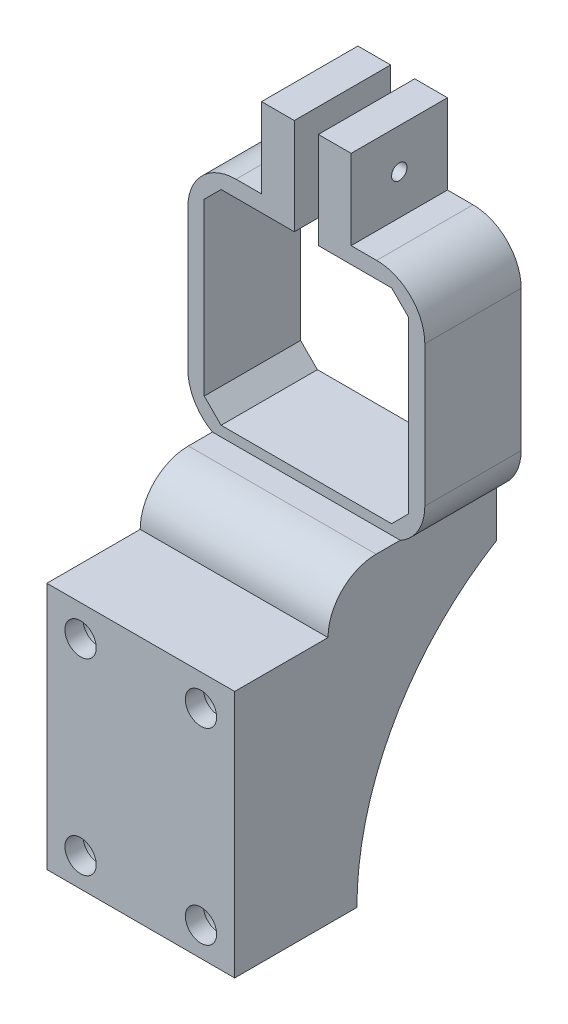
SolidWorks part; units mm, degrees
ref_plane "Front Plane" through (0, 0, 0) normal (0, 0, 1) x (1, 0, 0)
ref_plane "Top Plane" through (0, 0, 0) normal (0, 1, 0) x (1, 0, 0)
ref_plane "Right Plane" through (0, 0, 0) normal (1, 0, 0) x (0, 0, -1)
sketch "Sketch1" plane through (0, 0, 0) normal (0, 0, 1) x (1, 0, 0)
  line L1 (-21.2, -21.2) -> (21.2, -21.2)
  line L2 (-21.2, -21.2) -> (-21.2, 21.2)
  line L3 (-21.2, 21.2) -> (21.2, 21.2)
  line L4 (21.2, -21.2) -> (21.2, 21.2)
  line L5 (-21.2, -21.2) -> (21.2, 21.2) construction
  line L6 (-21.2, 21.2) -> (21.2, -21.2) construction
  line L7 (-24.6, -24.6) -> (24.6, -24.6)
  line L8 (-24.6, -24.6) -> (-24.6, 24.6)
  line L9 (-24.6, 24.6) -> (24.6, 24.6)
  line L10 (24.6, -24.6) -> (24.6, 24.6)
  line L11 (-24.6, -24.6) -> (24.6, 24.6) construction
  line L12 (-24.6, 24.6) -> (24.6, -24.6) construction
  point P0 (0, 0)
  point P5 (0, 0)
  dimension "D1" = 42.4
  dimension "D2" = 42.4
  dimension "D3" = 49.2
  dimension "D4" = 49.2
extrude "Boss-Extrude1" add sketch "Sketch1" along normal mid plane 20
chamfer "Chamfer1" distance 3.5 angle 45 4 edges at (21.2, -21.2, 0) (-21.2, -21.2, 0) (-21.2, 21.2, 0) (21.2, 21.2, 0)
fillet "Fillet1" radius 10 4 edges at (24.6, -24.6, 0) (-24.6, -24.6, 0) (-24.6, 24.6, 0) (24.6, 24.6, 0)
sketch "Sketch2" plane through (0, 0, 10) normal (0, 0, 1) x (1, 0, 0)
  line L5 (17.7, 21.2) -> (-17.7, 21.2) construction
  line L11 (-9.3, 17.8) -> (9.3, 17.8)
  line L12 (-9.3, 17.8) -> (-9.3, 24.6)
  line L17 (-9.3, 24.6) -> (9.3, 24.6)
  line L18 (9.3, 17.8) -> (9.3, 24.6)
  line L23 (-9.3, 17.8) -> (9.3, 24.6) construction
  line L24 (-9.3, 24.6) -> (9.3, 17.8) construction
  point P0 (0, 21.2)
  dimension "D1" = 6.8
  dimension "D2" = 18.6
extrude "Cut-Extrude1" cut sketch "Sketch2" against normal up to next
sketch "Sketch4" plane through (0, 21.2, 0) normal (0, -1, 0) x (1, 0, 0)
  line L1 (-9.3, -10) -> (-2.5, -10)
  line L2 (-9.3, -10) -> (-9.3, 10)
  line L3 (-9.3, 10) -> (-2.5, 10)
  line L4 (-2.5, -10) -> (-2.5, 10)
  line L5 (-17.7, 10) -> (17.7, 10) construction
  line L7 (9.3, -10) -> (2.5, -10)
  line L8 (9.3, -10) -> (9.3, 10)
  line L9 (9.3, 10) -> (2.5, 10)
  line L10 (2.5, -10) -> (2.5, 10)
  dimension "D1" = 20
  dimension "D2" = 6.8
  dimension "D3" = 20
  dimension "D4" = 6.8
extrude "Boss-Extrude2" add sketch "Sketch4" against normal blind 20
sketch "Sketch5" plane through (9.3, 0, 0) normal (1, 0, 0) x (0, 0, -1)
  circle A0 centre (0, 32.9) radius 1.6
  dimension "D1" = 3.2
extrude "Cut-Extrude2" cut sketch "Sketch5" against normal through all
sketch "Sketch7" plane through (0, 0, 0) normal (0, 0, 1) x (1, 0, 0)
  line L0 (0, 9.494) -> (0, -58.694) construction
  line L6 (-19.5, -24.6) -> (-19.5, -84.8)
  line L7 (-19.5, -84.8) -> (19.5, -84.8)
  line L8 (19.5, -84.8) -> (19.5, -24.6)
  line L10 (-19.5, -24.6) -> (-19.5, -23.3172)
  line L11 (-19.5, -23.3172) -> (19.5, -23.2738)
  line L12 (19.5, -23.2738) -> (19.5, -24.6)
  arc A1 (-24.6, -14.6) -> (-14.6, -24.6) centre (-14.6, -14.6) ccw construction
  dimension "D1" = 39
  dimension "D3" = 60.2
extrude "Boss-Extrude3" add sketch "Sketch7" along normal blind 25
sketch "Sketch8" plane through (0, 0, 0) normal (0, 0, -1) x (-1, 0, 0)
  line L3 (-19.5, -23.3172) -> (19.5, -23.3172)
  line L4 (-19.5, -23.3172) -> (-19.5, -33.3172)
  line L5 (-19.5, -33.3172) -> (19.5, -33.3172)
  line L6 (19.5, -23.3172) -> (19.5, -33.3172)
  line L7 (19.5, -23.3172) -> (19.5, -84.8) construction
  arc A1 (-24.6, -14.6) -> (-14.6, -24.6) centre (-14.6, -14.6) ccw construction
  dimension "D1" = 10
  dimension "D2" = 39
extrude "Boss-Extrude4" add sketch "Sketch8" along normal blind 10
sketch "Sketch9" plane through (0, 0, 25) normal (0, 0, 1) x (1, 0, 0)
  line L1 (-19.5, -84.8) -> (19.5, -84.8) construction
  line L2 (-19.5, -84.8) -> (-19.5, -33.8) construction
  line L3 (-19.5, -33.8) -> (19.5, -33.8) construction
  line L4 (19.5, -84.8) -> (19.5, -33.8) construction
  line L5 (19.5, -84.8) -> (19.5, -23.2738) construction
  dimension "D1" = 51
  dimension "D2" = 39
fillet "Fillet3" radius 10 1 edges at (0, -23.2955, 25)
sketch "Sketch10" plane through (-19.5, 0, 0) normal (-1, 0, 0) x (0, 0, 1)
  line L0 (0, -33.3172) -> (25, -33.3172) construction
  line L1 (25, -84.8) -> (25, -33.8) construction
  line L7 (0, -84.8) -> (19, -84.8)
  line L8 (0, -84.8) -> (0, -33.3172)
  line L9 (0, -33.3172) -> (19, -33.3172)
  line L10 (19, -84.8) -> (19, -33.3172)
  dimension "D1" = 51.4828
  dimension "D2" = 19
  dimension "D3" = 25
extrude "Cut-Extrude3" cut sketch "Sketch10" against normal up to next
fillet "Fillet4" radius 60 1 edges at (0, -33.3172, 19)
sketch "Sketch11" plane through (0, 0, 25) normal (0, 0, 1) x (1, 0, 0)
  line L0 (-19.5, -84.8) -> (-19.5, -33.8) construction
  line L1 (-19.5, -33.8) -> (19.5, -33.8) construction
  line L2 (19.5, -84.8) -> (19.5, -33.8) construction
  line L3 (-19.5, -84.8) -> (19.5, -84.8) construction
  circle A0 centre (-12.5, -39.8) radius 3.25
  circle A1 centre (12.5, -39.8) radius 3.25
  circle A2 centre (-12.5, -78.8) radius 3.25
  circle A3 centre (12.5, -78.8) radius 3.25
  dimension "D1" = 6.5
  dimension "D2" = 7
  dimension "D3" = 6
  dimension "D4" = 7
  dimension "D5" = 6
extrude "Cut-Extrude4" cut sketch "Sketch11" against normal through all
sketch "Sketch15" plane through (0, 0, -10) normal (0, 0, -1) x (-1, 0, 0)
  circle A0 centre (-12.5, -39.8) radius 4.5
  circle A1 centre (12.5, -39.8) radius 4.5
  dimension "D1" = 9
  dimension "D2" = 9
extrude "Cut-Extrude6" cut sketch "Sketch15" against normal blind 31.25
sketch "Sketch16" plane through (0, 0, -10) normal (0, 0, -1) x (-1, 0, 0)
  circle A0 centre (-12.5, -78.8) radius 4.5
  circle A1 centre (12.5, -78.8) radius 4.5
  dimension "D1" = 9
  dimension "D2" = 9
extrude "Cut-Extrude7" cut sketch "Sketch16" against normal blind 31.25
sketch "Sketch17" plane through (0, 0, 25) normal (0, 0, 1) x (1, 0, 0)
  line L4 (19.5, -84.8) -> (19.5, -33.2738)
  line L5 (19.5, -33.2738) -> (-19.5, -33.3172)
  line L6 (-19.5, -33.3172) -> (-19.5, -84.8)
  line L7 (-19.5, -84.8) -> (19.5, -84.8)
  line L8 (19.5, -84.8) -> (19.5, -33.2738)
  line L9 (19.5, -33.2738) -> (-19.5, -33.3172)
  line L10 (-19.5, -33.3172) -> (-19.5, -84.8)
  line L11 (-19.5, -84.8) -> (19.5, -84.8)
  circle A0 centre (-12.5, -78.8) radius 3.25 construction
  circle A1 centre (12.5, -78.8) radius 3.25 construction
  circle A2 centre (12.5, -39.8) radius 3.25 construction
  circle A3 centre (-12.5, -39.8) radius 3.25 construction
  circle A4 centre (-12.5, -78.8) radius 3.25
  circle A5 centre (12.5, -78.8) radius 3.25
  circle A6 centre (12.5, -39.8) radius 3.25
  circle A7 centre (-12.5, -39.8) radius 3.25
  dimension "D1" = 0
extrude "Boss-Extrude5" add sketch "Sketch17" along normal blind 19.38
sketch "Sketch18" plane through (0, 0, 21.25) normal (0, 0, -1) x (-1, 0, 0)
  circle A0 centre (12.5, -78.8) radius 4.5 construction
  circle A1 centre (-12.5, -78.8) radius 4.5 construction
  circle A2 centre (12.5, -39.8) radius 4.5 construction
  circle A3 centre (-12.5, -39.8) radius 4.5 construction
  circle A4 centre (12.5, -78.8) radius 4.5
  circle A5 centre (-12.5, -78.8) radius 4.5
  circle A6 centre (12.5, -39.8) radius 4.5
  circle A7 centre (-12.5, -39.8) radius 4.5
extrude "Cut-Extrude8" cut sketch "Sketch18" against normal blind 19.38
